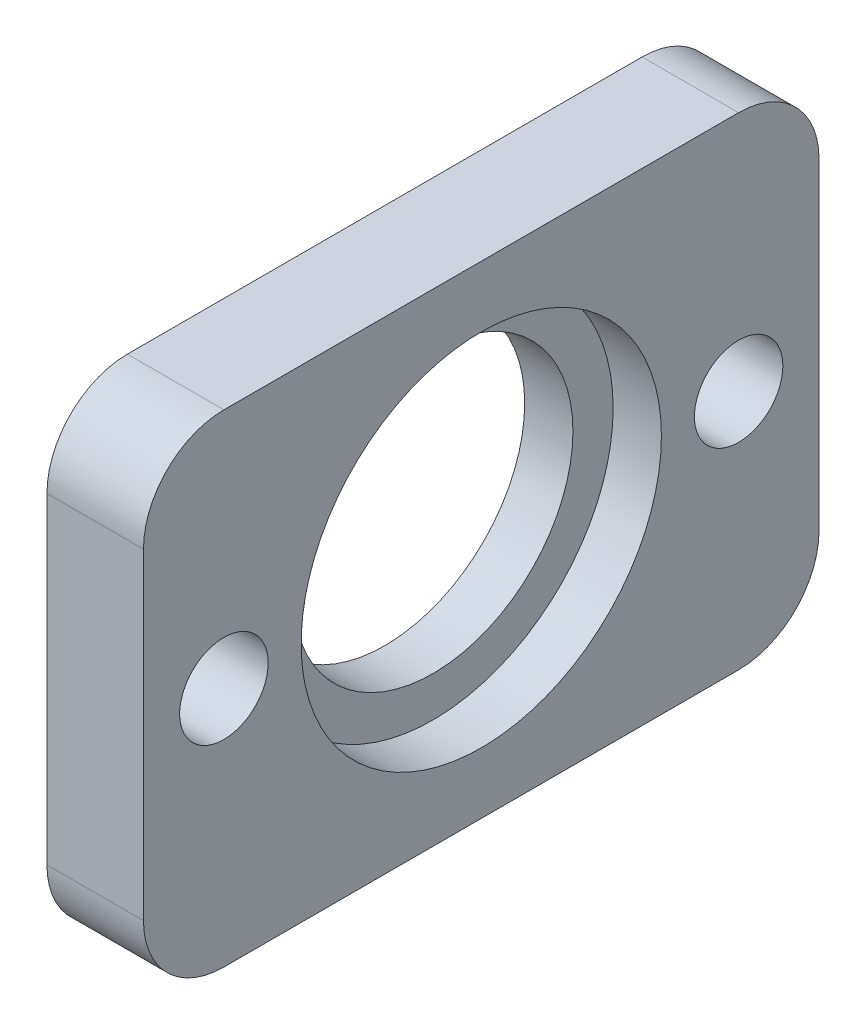
SolidWorks part; units mm, degrees
ref_plane "Ebene vorne" through (0, 0, 0) normal (0, 0, 1) x (1, 0, 0)
ref_plane "Ebene oben" through (0, 0, 0) normal (0, 1, 0) x (1, 0, 0)
ref_plane "Ebene rechts" through (0, 0, 0) normal (1, 0, 0) x (0, 0, -1)
sketch "Skizze1" plane through (0, 0, 0) normal (1, 0, 0) x (0, 0, -1)
  line L1 (21, -15) -> (-21, -15)
  line L2 (21, -15) -> (21, 15)
  line L3 (21, 15) -> (-21, 15)
  line L4 (-21, -15) -> (-21, 15)
  line L5 (21, -15) -> (-21, 15) construction
  line L6 (21, 15) -> (-21, -15) construction
  circle A0 centre (0, 0) radius 11.2
  circle A1 centre (0, 0) radius 8.7
  point P0 (0, 0)
  dimension "D1" = 17.4
  dimension "D2" = 22.4
  dimension "D3" = 42
  dimension "D4" = 30
extrude "Aufsatz-Linear austragen1" add sketch "Skizze1" against normal blind 6 contours L3 L4 L1 L2
extrude "Schnitt-Linear austragen1" cut sketch "Skizze1<3>" against normal blind 6 contours A1 | A1 region at (0, 0, 0)
sketch "Skizze1<3>" plane through (0, 0, 0) normal (1, 0, 0) x (0, 0, -1) same geometry as "Skizze1"
extrude "Schnitt-Linear austragen2" cut sketch "Skizze1<4>" against normal blind 3 contours A0
sketch "Skizze1<4>" plane through (0, 0, 0) normal (1, 0, 0) x (0, 0, -1) same geometry as "Skizze1"
hole_wizard "Ø5.5 (5.5) Durchmesser Bohrung1" positions "Skizze5" profile "Skizze4" hole size "Ø5.5" standard "ISO" end condition through all
sketch "Skizze5" plane through (0, 0, 0) normal (1, 0, 0) x (0, 0, -1)
  line L2 (-16, 0) -> (16, 0) construction
  point P0 (-16, 0)
  point P19 (16, 0)
  dimension "D1" = 32
  dimension "D2" = 16
sketch "Skizze4" plane through (0, 0, 16) normal (0, 1, 0) x (0, 0, -1)
  line L0 (0, 0) -> (0, 6)
  line L1 (0, 6) -> (2.75, 6)
  line L2 (2.75, 6) -> (2.75, 0)
  line L5 (2.75, 0) -> (0, 0)
  line L11 (0, -6.35) -> (0, 107.95) construction
  dimension "Bohrerdurchmesser" = 5.5
  dimension "Bohrungstiefe" = 6
fillet "Verrundung1" radius 5 4 edges at (-3, 15, 21) (-3, 15, -21) (-3, -15, -21) (-3, -15, 21)
